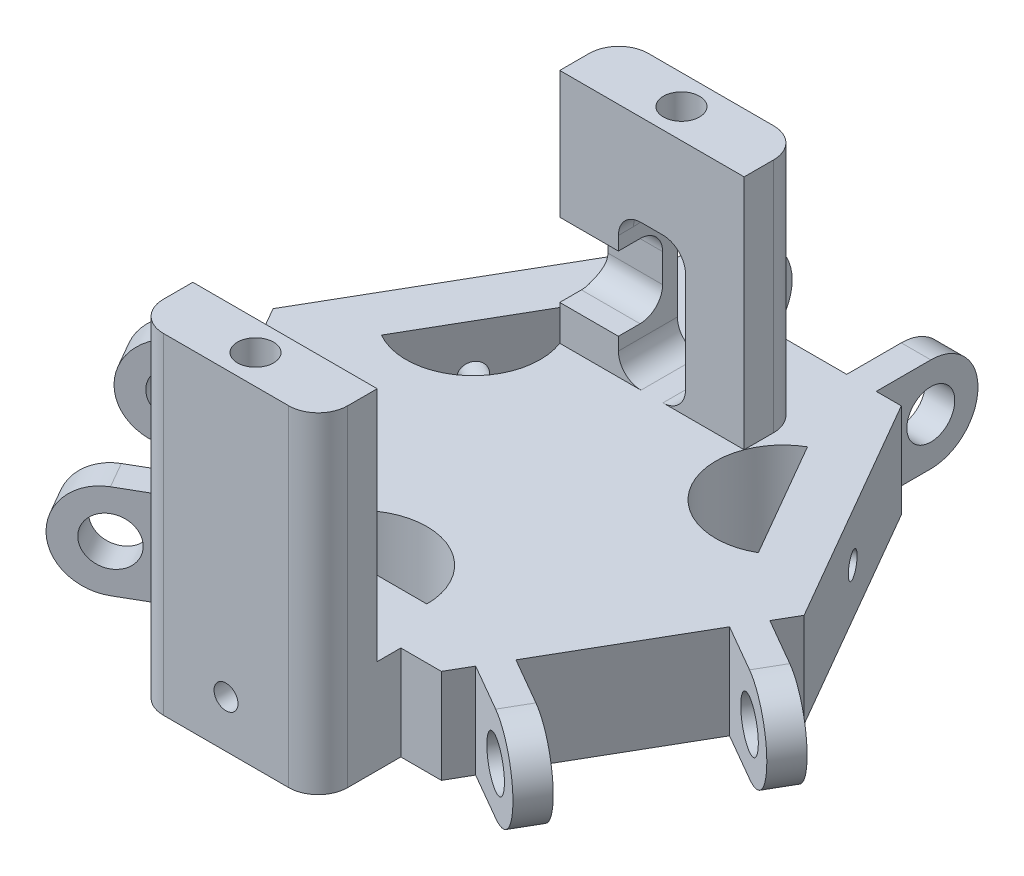
SolidWorks part; units mm, degrees
ref_plane "Piano frontale" through (0, 0, 0) normal (0, 0, 1) x (1, 0, 0)
ref_plane "Piano superiore" through (0, 0, 0) normal (0, 1, 0) x (1, 0, 0)
ref_plane "Piano destro" through (0, 0, 0) normal (1, 0, 0) x (0, 0, -1)
sketch "Schizzo1" plane through (0, 0, 0) normal (0, 1, 0) x (1, 0, 0)
  line L0 (-25.9007, 0) -> (24.7765, 0) construction
  line L1 (18, 0) -> (9, 15.5885)
  line L2 (9, 15.5885) -> (-9, 15.5885)
  line L3 (-9, 15.5885) -> (-18, 0)
  line L4 (-18, 0) -> (-9, -15.5885)
  line L5 (-9, -15.5885) -> (9, -15.5885)
  line L6 (9, -15.5885) -> (18, 0)
  circle A0 centre (0, 0) radius 15.5885 construction
  dimension "D1" = 18
extrude "Estrusione-Estrusione1" add sketch "Schizzo1" along normal blind 6.4
sketch "Schizzo2" plane through (0, 6.4, 0) normal (0, 1, 0) x (1, 0, 0)
  line L0 (-4.55, -12.125) -> (4.55, -12.125)
  line L1 (-7.6422, 0) -> (9.3711, 0) construction
  line L2 (0, 2.5203) -> (0, -4.0345) construction
  arc A0 (-4.55, -12.125) -> (4.55, -12.125) centre (0, -12.125) cw
  dimension "D2" = 4.55
  dimension "D1" = 12.125
ref_axis "Assi1" through (0, -0.32, 0) along (0, 1, 0)
extrude "Taglio-Estrusione1" cut sketch "Schizzo2" against normal up to next
sketch "Schizzo3" plane through (-13.5, 0, 7.7942) normal (-0.866, 0, 0.5) x (0.5, 0, 0.866)
  line L0 (-9, 0) -> (9, 0) construction
  line L1 (-7.3, 6.4) -> (-5.3, 6.4)
  line L2 (-7.3, 6.4) -> (-7.3, 0)
  line L3 (-7.3, 0) -> (-5.3, 0)
  line L4 (-5.3, 6.4) -> (-5.3, 0)
  line L6 (7.3, 6.4) -> (5.3, 6.4)
  line L7 (7.3, 6.4) -> (7.3, 0)
  line L8 (7.3, 0) -> (5.3, 0)
  line L9 (5.3, 6.4) -> (5.3, 0)
  line L10 (-9, 6.4) -> (9, 6.4) construction
  line L11 (0, 0) -> (0, 6.4) construction
  dimension "D1" = 2
  dimension "D2" = 10.6
extrude "Estrusione-Estrusione2" add sketch "Schizzo3" along normal blind 6.9
sketch "Schizzo4" plane through (3.65, 0, 6.322) normal (0.5, 0, 0.866) x (0.866, 0, -0.5)
  line L3 (-15.5885, 0) -> (-15.5885, 6.4) construction
  line L10 (-22.4885, 6.4) -> (-15.5885, 6.4) construction
  line L11 (-22.4885, 0) -> (-15.5885, 0) construction
  line L12 (-19.2885, 6.4) -> (-19.2885, 0) construction
  circle A0 centre (-19.2885, 3.2) radius 1.625
  dimension "D1" = 3.25
  dimension "D2" = 3.7
extrude "Taglio-Estrusione2" cut sketch "Schizzo4" against normal up to surface (14.6 mm away) up to face at (-20.1378, 3.2, 3.1972)
fillet "Raccordo2" 2 edges at (-22.6256, 6.4, 5.7883) (-22.6256, 0, 5.7883) type full round first side face at (0, 6.4, 9.85) second side face at (0, 0, 9.85) middle face at (-22.6256, 3.2, 5.7883)
fillet "Raccordo3" 2 edges at (-16.3256, 6.4, 16.7002) (-16.3256, 0, 16.7002) type full round first side face at (0, 6.4, 9.85) second side face at (0, 0, 9.85) middle face at (-16.3256, 3.2, 16.7002)
sketch "Schizzo5" plane through (0, 0, 15.5885) normal (0, 0, 1) x (1, 0, 0)
  line L0 (0, 0) -> (0, 6.4) construction
  line L1 (-9, 0) -> (9, 0) construction
  line L2 (-9, 6.4) -> (9, 6.4) construction
  circle A0 centre (0, 3.2) radius 0.8125
  dimension "D1" = 1.625
extrude "Taglio-Estrusione3" cut sketch "Schizzo5" against normal up to next
pattern_circular "RipetizioneCircolare1" count 3 every 120 about axis through (0, -0.32, 0) along (0, 1, 0) of "Estrusione-Estrusione2", "Taglio-Estrusione1", "Taglio-Estrusione2", "Raccordo2", "Raccordo3", "Taglio-Estrusione3"
sketch "Schizzo6" plane through (0, 0, 15.5885) normal (0, 0, 1) x (1, 0, 0)
  line L0 (-9, 6.4) -> (9, 6.4) construction
  line L1 (-6.25, 6.4) -> (6.25, 6.4)
  line L2 (-6.25, 6.4) -> (-6.25, 0)
  line L3 (-6.25, 0) -> (6.25, 0)
  line L4 (6.25, 6.4) -> (6.25, 0)
  line L5 (-9, 0) -> (9, 0) construction
  line L6 (0, -0.4417) -> (0, 6.8417) construction
  circle A0 centre (0, 3.2) radius 0.8125
  circle A1 centre (0, 3.2) radius 0.8125 construction
  point P11 (0, 6.4)
  dimension "D1" = 12.5
extrude "Estrusione-Estrusione3" add sketch "Schizzo6" along normal blind 5.6
sketch "Schizzo7" plane through (0, 6.4, 0) normal (0, 1, 0) x (1, 0, 0)
  line L0 (-6.25, -21.1885) -> (-6.25, -15.5885) construction
  line L1 (-6.25, -17.1885) -> (6.25, -17.1885)
  line L2 (-6.25, -17.1885) -> (-6.25, -21.1885)
  line L3 (-6.25, -21.1885) -> (6.25, -21.1885)
  line L4 (6.25, -17.1885) -> (6.25, -21.1885)
  line L6 (6.25, 7.6858) -> (-6.25, 7.6858)
  line L7 (6.25, 7.6858) -> (6.25, 11.6858)
  line L8 (6.25, 11.6858) -> (-6.25, 11.6858)
  line L9 (-6.25, 7.6858) -> (-6.25, 11.6858)
  arc A0 (-12.7756, 2.1221) -> (-8.2256, 10.0029) centre (-10.5006, 6.0625) ccw construction
  dimension "D1" = 4
extrude "Estrusione-Estrusione4" add sketch "Schizzo7" along normal blind 16.02
fillet "Raccordo4" radius 2 4 edges at (6.25, 11.21, 21.1885) (-6.25, 11.21, 21.1885) (6.25, 14.41, -11.6858) (-6.25, 14.41, -11.6858)
sketch "Schizzo8" plane through (0, 22.42, 0) normal (0, 1, 0) x (1, 0, 0)
  line L0 (0, -33.7522) -> (0, 14.7049) construction
  line L3 (-6.25, -19.1885) -> (6.25, -19.1885) construction
  line L4 (-6.25, -17.1885) -> (-6.25, -19.1885) construction
  line L5 (6.25, -19.1885) -> (6.25, -17.1885) construction
  line L6 (6.25, 9.6858) -> (-6.25, 9.6858) construction
  circle A0 centre (0, -19.1885) radius 1.225
  circle A1 centre (0, 9.6858) radius 1.225
  arc A2 (4.25, -21.1885) -> (6.25, -19.1885) centre (4.25, -19.1885) ccw construction
  arc A3 (-4.25, 11.6858) -> (-6.25, 9.6858) centre (-4.25, 9.6858) ccw construction
  dimension "D1" = 2.45
extrude "Taglio-Estrusione4" cut sketch "Schizzo8" against normal blind 9
sketch "Schizzo9" plane through (0, 0, -11.6858) normal (0, 0, -1) x (-1, 0, 0)
  line L0 (-4.25, 6.4) -> (4.25, 6.4) construction
  line L1 (2.275, 16.25) -> (-2.275, 16.25)
  line L2 (2.275, 16.25) -> (2.275, 6.4)
  line L3 (2.275, 6.4) -> (-2.275, 6.4)
  line L4 (-2.275, 16.25) -> (-2.275, 6.4)
  line L5 (0, -0.32) -> (0, 6.72) construction
  point P9 (0, 16.25)
  dimension "D1" = 9.85
  dimension "D2" = 4.55
extrude "Taglio-Estrusione5" cut sketch "Schizzo9" against normal up to next
sketch "Schizzo11" plane through (-6.25, 0, 0) normal (-1, 0, 0) x (0, 0, 1)
  line L0 (-7.6858, 22.42) -> (-7.6858, 6.4) construction
  line L1 (-7.6858, 8.8) -> (-10.6847, 8.8)
  line L2 (-7.6858, 8.8) -> (-7.6858, 13.8)
  line L3 (-7.6858, 13.8) -> (-10.6847, 13.8)
  line L4 (-10.6847, 8.8) -> (-10.6847, 13.8)
  line L5 (-9.6858, 6.4) -> (-7.6858, 6.4) construction
  point P6 (-9.1853, 8.8)
  dimension "D1" = 5
  dimension "D2" = 2.4
extrude "Taglio-Estrusione6" cut sketch "Schizzo11" against normal up to surface (3.975 mm away) up to face at (-2.275, 11.325, -9.6858)
fillet "Raccordo5" radius 1.53 6 edges at (2.275, 16.25, -9.6858) (-4.1289, 13.8, -10.6847) (-4.1289, 8.8, -10.6847) (-2.275, 16.25, -9.6858) (2.275, 6.4, -9.6858) (-2.275, 6.4, -9.6858)
